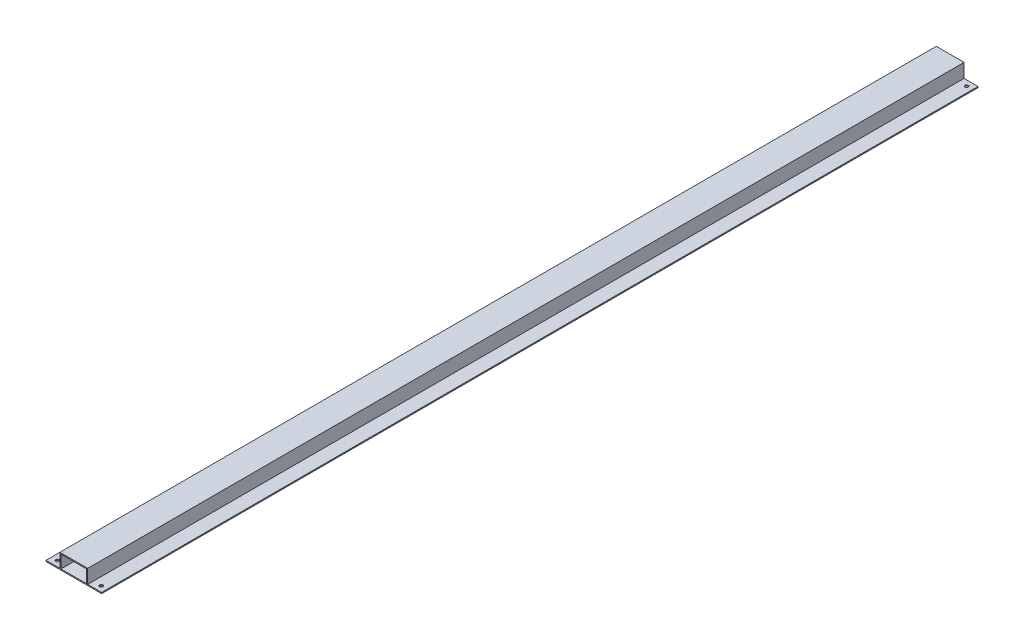
SolidWorks part; units mm, degrees
ref_plane "Alzado" through (0, 0, 0) normal (0, 0, 1) x (1, 0, 0)
ref_plane "Planta" through (0, 0, 0) normal (0, 1, 0) x (1, 0, 0)
ref_plane "Vista lateral" through (0, 0, 0) normal (1, 0, 0) x (0, 0, -1)
sketch "Croquis1" plane through (0, 0, 0) normal (0, 0, 1) x (1, 0, 0)
  line L0 (0, 31.0221) -> (0, -31.113) construction
  line L1 (38.9974, 0) -> (-46.5113, 0) construction
  line L2 (0, 12.7) -> (-11.7, 12.7)
  line L3 (0, 13.7) -> (-12.7, 13.7)
  line L4 (0, 13.7) -> (0, 1) construction
  line L5 (11.7, 1) -> (-11.7, 1)
  line L6 (-12.7, 13.7) -> (-12.7, 1)
  line L7 (25.4, 0) -> (-25.4, 0)
  line L8 (0, 0) -> (0, 1) construction
  line L9 (11.7, 1) -> (-11.7, 1)
  line L10 (-25.4, 0) -> (-25.4, 1)
  line L11 (-11.7, 12.7) -> (-11.7, 1)
  line L12 (-12.7, 1) -> (-25.4, 1)
  line L13 (12.7, 1) -> (25.4, 1)
  line L14 (11.7, 12.7) -> (11.7, 1)
  line L15 (25.4, 0) -> (25.4, 1)
  line L16 (12.7, 13.7) -> (12.7, 1)
  line L17 (0, 13.7) -> (12.7, 13.7)
  line L18 (0, 12.7) -> (11.7, 12.7)
  dimension "D1" = 12.7
  dimension "D2" = 12.7
  dimension "D3" = 1
  dimension "D4" = 1
  dimension "D5" = 25.4
extrude "Saliente-Extruir1" add sketch "Croquis1" along normal mid plane 800 contours L17 L3 L6 L12 L10 L7 L15 L13 L16 L2 L18 L14 L5 L11 region at (6.35, 13.1739, 0)
sketch "Croquis2" plane through (0, 0, 0) normal (0, -1, 0) x (1, 0, 0)
  line L0 (0, 512.6061) -> (0, -444.1411) construction
  line L1 (-90.5126, 0) -> (85.6051, 0) construction
  line L2 (-20, 395) -> (20, 395) construction
  line L3 (-20, 395) -> (-20, -395) construction
  circle A0 centre (-20, 395) radius 1.5
  circle A1 centre (20, 395) radius 1.5
  circle A2 centre (20, -395) radius 1.5
  circle A3 centre (-20, -395) radius 1.5
  dimension "D2" = 3
  dimension "D1" = 20
  dimension "D3" = 395
  dimension "D6" = 90
  dimension "D7" = 40
  dimension "D8" = 790
  dimension "D4" = 2
  dimension "D5" = 2
extrude "Cortar-Extruir1" cut sketch "Croquis2" against normal blind 10
